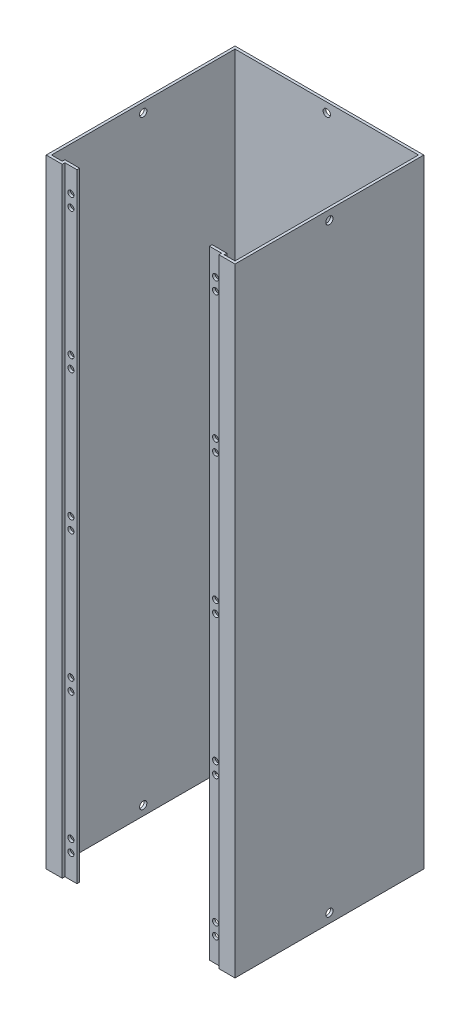
SolidWorks part; units mm, degrees
ref_plane "Front Plane" through (0, 0, 0) normal (0, 0, 1) x (1, 0, 0)
ref_plane "Top Plane" through (0, 0, 0) normal (0, 1, 0) x (1, 0, 0)
ref_plane "Right Plane" through (0, 0, 0) normal (1, 0, 0) x (0, 0, -1)
sketch "Sketch1" plane through (0, 0, 0) normal (0, 1, 0) x (1, 0, 0)
  line L0 (0, 0) -> (0, 100)
  line L1 (0, 100) -> (100, 100)
  line L2 (100, 100) -> (100, 0)
  line L3 (100, 0) -> (91.5, 0)
  line L4 (91.5, 0) -> (91.5, 1.397)
  line L5 (91.5, 1.397) -> (85.1, 1.397)
  line L6 (85.1, 1.397) -> (85.1, 2.794)
  line L7 (85.1, 2.794) -> (92.897, 2.794)
  line L8 (92.897, 2.794) -> (92.897, 1.397)
  line L9 (92.897, 1.397) -> (98.603, 1.397)
  line L10 (98.603, 1.397) -> (98.603, 98.603)
  line L11 (98.603, 98.603) -> (1.397, 98.603)
  line L12 (1.397, 98.603) -> (1.397, 1.397)
  line L13 (1.397, 1.397) -> (7.103, 1.397)
  line L14 (7.103, 1.397) -> (7.103, 2.794)
  line L15 (7.103, 2.794) -> (14.9, 2.794)
  line L16 (14.9, 2.794) -> (14.9, 1.397)
  line L17 (14.9, 1.397) -> (8.5, 1.397)
  line L18 (8.5, 1.397) -> (8.5, 0)
  line L19 (8.5, 0) -> (0, 0)
  dimension "D1" = 8.5
  dimension "D2" = 8.5
  dimension "D3" = 100
  dimension "D4" = 100
  dimension "D5" = 1.397
  dimension "D6" = 7.797
  dimension "D7" = 5.706
  dimension "D8" = 6.4
  dimension "D9" = 1.397
  dimension "D10" = 1.397
  dimension "D11" = 1.397
  dimension "D12" = 1.397
  dimension "D13" = 1.397
  dimension "D14" = 14.9
  dimension "D15" = 14.9
  dimension "D16" = 0
  dimension "D17" = 0
  dimension "D18" = 1.397
extrude "Boss-Extrude1" add sketch "Sketch1" along normal blind 327.5
sketch "Sketch2" plane through (0, 0, -1.397) normal (0, 0, 1) x (1, 0, 0)
  line L0 (8.5, 327.5) -> (14.9, 327.5) construction
  line L1 (14.9, 327.5) -> (14.9, 0) construction
  line L2 (85.1, 327.5) -> (85.1, 0) construction
  line L3 (85.1, 327.5) -> (91.5, 327.5) construction
  line L4 (8.5, 0) -> (14.9, 0) construction
  circle A0 centre (11.7, 314.9) radius 1.6
  circle A1 centre (11.7, 308.5) radius 1.6
  circle A2 centre (88.3, 314.9) radius 1.6
  circle A3 centre (88.3, 308.5) radius 1.6
  circle A4 centre (11.7, 240.925) radius 1.6
  circle A5 centre (11.7, 234.525) radius 1.6
  circle A6 centre (88.3, 240.925) radius 1.6
  circle A7 centre (88.3, 234.525) radius 1.6
  circle A8 centre (11.7, 166.95) radius 1.6
  circle A9 centre (11.7, 160.55) radius 1.6
  circle A10 centre (88.3, 166.95) radius 1.6
  circle A11 centre (88.3, 160.55) radius 1.6
  circle A12 centre (11.7, 92.975) radius 1.6
  circle A13 centre (11.7, 86.575) radius 1.6
  circle A14 centre (88.3, 92.975) radius 1.6
  circle A15 centre (88.3, 86.575) radius 1.6
  circle A16 centre (11.7, 19) radius 1.6
  circle A17 centre (11.7, 12.6) radius 1.6
  circle A18 centre (88.3, 19) radius 1.6
  circle A19 centre (88.3, 12.6) radius 1.6
  dimension "D1" = 3.2
  dimension "D2" = 3.2
  dimension "D3" = 12.6
  dimension "D4" = 6.4
  dimension "D5" = 3.2
  dimension "D6" = 3.2
  dimension "D8" = 3.2
  dimension "D9" = 3.2
  dimension "D10" = 12.6
  dimension "D12" = 12.6
  dimension "D7" = 2
  dimension "D11" = 5
extrude "Cut-Extrude2" cut sketch "Sketch2" against normal blind 10
sketch "Sketch3" plane through (100, 0, 0) normal (1, 0, 0) x (0, 0, -1)
  line L0 (0, 327.5) -> (100, 327.5) construction
  line L1 (0, 327.5) -> (0, 0) construction
  line L2 (100, 327.5) -> (100, 0) construction
  line L3 (0, 0) -> (100, 0) construction
  circle A0 centre (50, 322.524) radius 1.93
  circle A1 centre (50, 4.976) radius 1.93
  dimension "D1" = 3.86
  dimension "D7" = 3.86
  dimension "D2" = 4.976
  dimension "D3" = 50
  dimension "D4" = 50
  dimension "D5" = 50
  dimension "D6" = 4.976
extrude "Cut-Extrude3" cut sketch "Sketch3" against normal blind 100
sketch "Sketch4" plane through (0, 0, -100) normal (0, 0, -1) x (-1, 0, 0)
  line L0 (-100, 327.5) -> (0, 327.5) construction
  line L1 (0, 327.5) -> (0, 0) construction
  line L2 (-100, 0) -> (0, 0) construction
  circle A0 centre (-50, 322.524) radius 1.93
  circle A1 centre (-50, 4.976) radius 1.93
  dimension "D1" = 3.86
  dimension "D2" = 3.86
  dimension "D3" = 4.976
  dimension "D4" = 50
  dimension "D5" = 4.976
  dimension "D6" = 50
extrude "Cut-Extrude4" cut sketch "Sketch4" against normal blind 10
